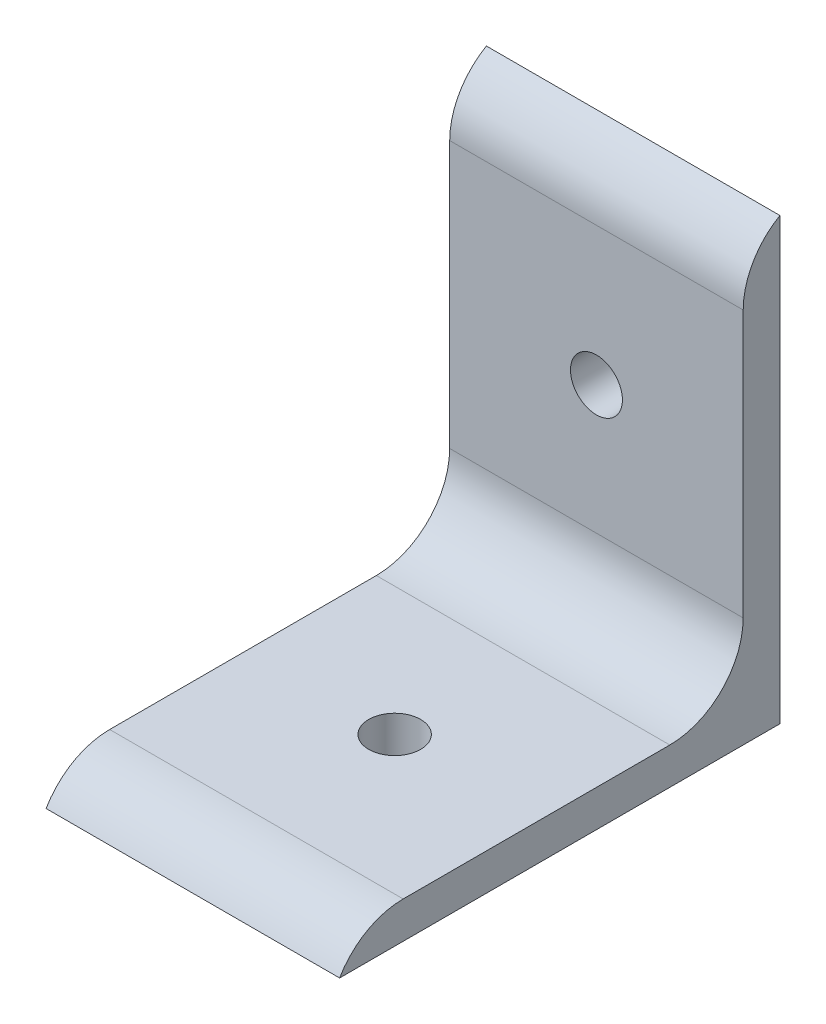
SolidWorks part; units mm, degrees
ref_plane "Front Plane" through (0, 0, 0) normal (0, 0, 1) x (1, 0, 0)
ref_plane "Top Plane" through (0, 0, 0) normal (0, 1, 0) x (1, 0, 0)
ref_plane "Right Plane" through (0, 0, 0) normal (1, 0, 0) x (0, 0, -1)
sketch "Sketch1" plane through (0, 0, 0) normal (1, 0, 0) x (0, 0, -1)
  line L0 (0, 0) -> (0, 38.1)
  line L9 (0, 38.1) -> (-3.175, 38.1)
  line L10 (-3.175, 38.1) -> (-3.175, 3.175)
  line L11 (-3.175, 3.175) -> (-38.1, 3.175)
  line L12 (-38.1, 3.175) -> (-38.1, 0)
  line L13 (-38.1, 0) -> (0, 0)
  dimension "D1" = 38.1
  dimension "D2" = 38.1
  dimension "D3" = 3.175
  dimension "D4" = 3.175
extrude "Boss-Extrude1" add sketch "Sketch1" along normal blind 25.4
sketch "Sketch2" plane through (0, 0, 3.175) normal (0, 0, 1) x (1, 0, 0)
  line L0 (12.7, 3.175) -> (12.7, 38.1) construction
  line L1 (25.4, 3.175) -> (0, 3.175) construction
  line L2 (25.4, 38.1) -> (0, 38.1) construction
  line L3 (25.4, 20.6375) -> (0, 20.6375) construction
  line L4 (25.4, 38.1) -> (25.4, 3.175) construction
  line L5 (0, 38.1) -> (0, 3.175) construction
  point P12 (12.7, 20.6375)
sketch "Sketch3" plane through (0, 3.175, 0) normal (0, 1, 0) x (1, 0, 0)
  line L0 (25.4, -3.175) -> (0, -3.175) construction
  line L1 (0, -38.1) -> (25.4, -38.1)
  line L2 (0, -38.1) -> (0, -3.175)
  line L3 (0, -3.175) -> (25.4, -3.175)
  line L4 (25.4, -38.1) -> (25.4, -3.175)
  line L5 (0, -38.1) -> (25.4, -3.175) construction
  line L6 (0, -3.175) -> (25.4, -38.1) construction
  line L7 (25.4, -3.175) -> (25.4, -38.1) construction
  line L8 (0, -3.175) -> (0, -38.1) construction
  line L9 (25.4, -38.1) -> (0, -38.1) construction
  point P0 (12.7, -20.6375)
  point P13 (12.7, -20.6375)
fillet "Fillet1" radius 6.35 3 edges at (12.7, 38.1, 3.175) (12.7, 3.175, 38.1) (12.7, 3.175, 3.175)
hole_wizard "#8 Clearance Hole1" positions "Sketch4" profile "Sketch5" hole size "#8" standard "ANSI Inch" end condition through all
sketch "Sketch4" plane through (0, 0, 3.175) normal (0, 0, 1) x (1, 0, 0)
  point P0 (12.7, 20.6375)
sketch "Sketch5" plane through (12.7, 20.6375, 3.175) normal (1, 0, 0) x (0, -1, 0)
  line L0 (0, 0) -> (0, 3.175)
  line L1 (0, 3.175) -> (2.2479, 3.175)
  line L2 (2.2479, 3.175) -> (2.2479, 0)
  line L5 (2.2479, 0) -> (0, 0)
  line L11 (0, -6.35) -> (0, 107.95) construction
  dimension "Thru Hole Dia." = 4.4958
  dimension "Thru Hole Depth" = 3.175
hole_wizard "#8 Clearance Hole2" positions "Sketch6" profile "Sketch7" hole size "#8" standard "ANSI Inch" end condition through all
sketch "Sketch6" plane through (0, 3.175, 0) normal (0, 1, 0) x (1, 0, 0)
  point P0 (12.7, -20.6375)
sketch "Sketch7" plane through (12.7, 3.175, 20.6375) normal (1, 0, 0) x (0, 0, 1)
  line L0 (0, 0) -> (0, 3.175)
  line L1 (0, 3.175) -> (2.2479, 3.175)
  line L2 (2.2479, 3.175) -> (2.2479, 0)
  line L5 (2.2479, 0) -> (0, 0)
  line L11 (0, -6.35) -> (0, 107.95) construction
  dimension "Thru Hole Dia." = 4.4958
  dimension "Thru Hole Depth" = 3.175
sketch "Sketch8" plane through (0, 0, 0) normal (0, 0, -1) x (-1, 0, 0)
  line L0 (-25.4, 0) -> (0, 0) construction
  point P0 (-12.7, 0)
